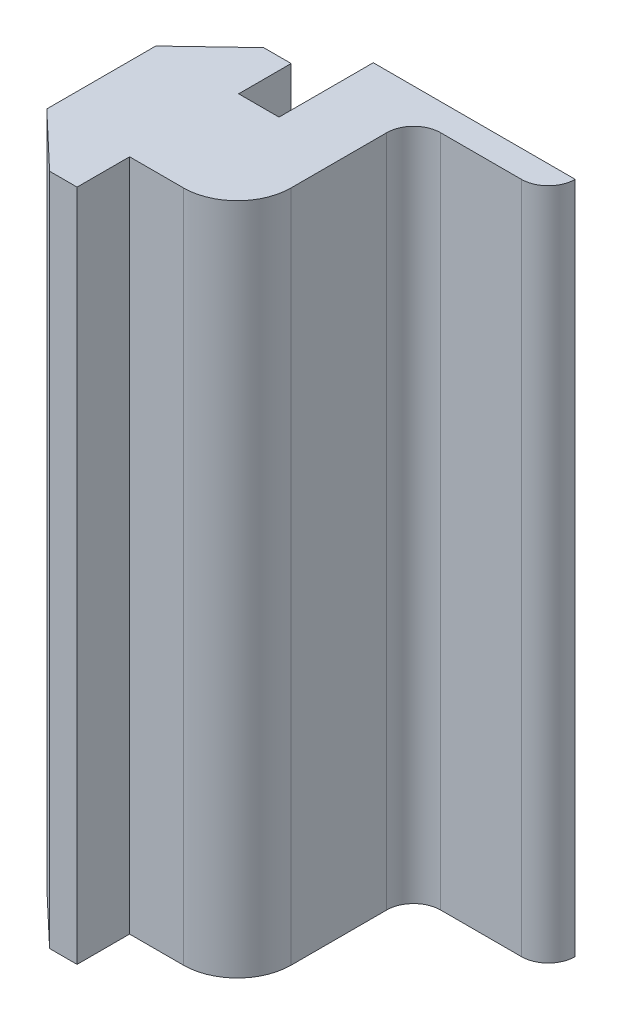
SolidWorks part; units mm, degrees
ref_plane "Front Plane" through (0, 0, 0) normal (0, 0, 1) x (1, 0, 0)
ref_plane "Top Plane" through (0, 0, 0) normal (0, 1, 0) x (1, 0, 0)
ref_plane "Right Plane" through (0, 0, 0) normal (1, 0, 0) x (0, 0, -1)
sketch "Sketch1" plane through (0, 0, 0) normal (0, 1, 0) x (1, 0, 0)
  line L0 (0, 4.05) -> (8, 4.05)
  line L1 (0, -4.05) -> (8, -4.05)
  line L2 (8, -4.05) -> (8, 4.05)
  line L3 (8, 4.05) -> (8, 11.05)
  line L4 (8, 11.05) -> (3, 11.05)
  line L5 (3, 11.05) -> (3, 4.05)
  line L6 (8, 11.05) -> (18, 11.05)
  line L7 (18, 11.05) -> (18, 9.05)
  line L8 (18, 9.05) -> (8, 9.05)
  line B0 (0, -7.95) -> (-2.04, -7.95)
  line B1 (-6.1524, -4.048) -> (-6.1524, 4.048)
  line B2 (-2.04, 7.95) -> (0, 7.95)
  line B3 (0, 7.95) -> (0, -7.95)
  line B4 (-2.04, -7.95) -> (-6.1524, -4.048)
  line B5 (-6.1524, 4.048) -> (-2.04, 7.95)
  line B6 (0, -4.05) -> (0, 4.05) construction
  dimension "D1" = 8
  dimension "D2" = 5
  dimension "D3" = 7
  dimension "D4" = 10
  dimension "D5" = 2
sketch_block_instance "Extrusion Profile-2"
sketch_block "Extrusion Profile" parameters "D1"=8.44, "D2"=2.6, "D3"=6, "D4"=16.7, "D6"=5.6686, "D7"=2.0404, "D8"=8.0963, "D9"=15.9, "D5"=2.4157
extrude "Boss-Extrude1" add sketch "Sketch1" along normal blind 50 contours L0 B3 L1 L2 | L4 L5 L0 L3 | B2 B5 B1 B4 B0 B3 | L8 L7 L6 L3 region at (-2.7416, 0, 0) region at (4, 0, 0) region at (5.5, 0, -7.55) region at (13, 0, -10.05)
fillet "Fillet1" radius 2 1 edges at (8, 25, -9.05)
fillet "Fillet2" radius 4 1 edges at (8, 25, 4.05)
fillet "Fillet3" radius 2 1 edges at (18, 25, -9.05)
